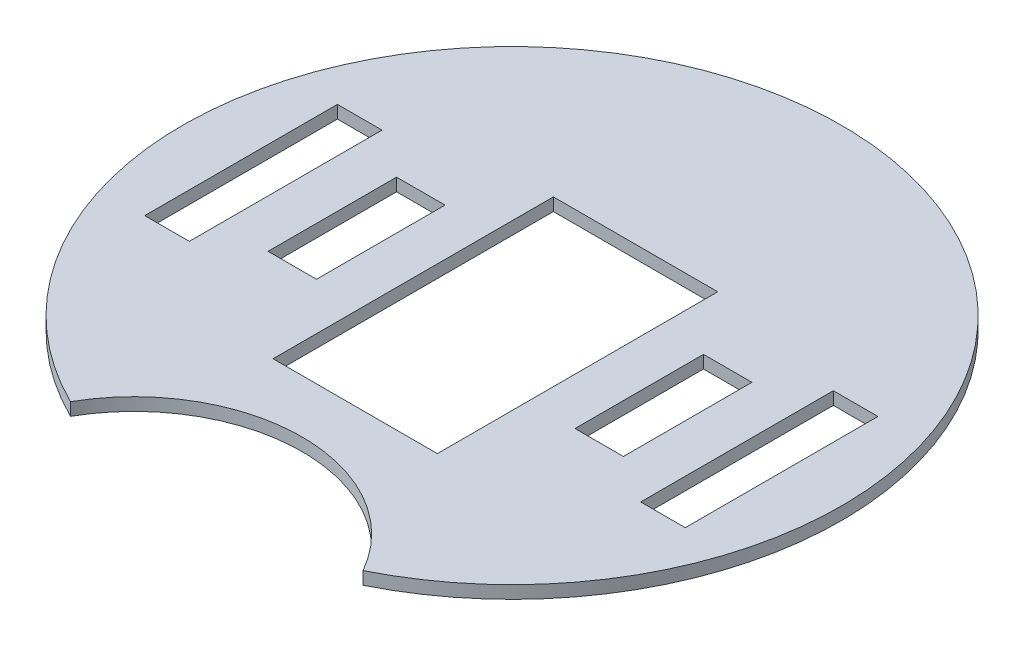
SolidWorks part; units mm, degrees
ref_plane "Front Plane" through (0, 0, 0) normal (0, 0, 1) x (1, 0, 0)
ref_plane "Top Plane" through (0, 0, 0) normal (0, 1, 0) x (1, 0, 0)
ref_plane "Right Plane" through (0, 0, 0) normal (1, 0, 0) x (0, 0, -1)
sketch "Sketch1" plane through (0, 0, 0) normal (0, 1, 0) x (1, 0, 0)
  line L0 (0, -86.0416) -> (-33.2911, -67.2064) construction
  line L1 (0, -86.0416) -> (0, 0) construction
  arc A0 (33.2911, -67.2064) -> (-33.2911, -67.2064) centre (0, 0) ccw
  arc A1 (33.2911, -67.2064) -> (-33.2911, -67.2064) centre (0, -86.0416) ccw
  dimension "D1" = 150
  dimension "D2" = 76.5
  dimension "D3" = 60.5
extrude "Boss-Extrude1" add sketch "Sketch1" along normal blind 2.9
sketch "solenoid placement" plane through (0, 2.9, 0) normal (0, 1, 0) x (1, 0, 0)
  line L0 (0, 0) -> (0, -36) construction
  line L1 (0, -36) -> (0, -47.7916) construction
  line L2 (-19, -36) -> (19, -36) construction
  line L3 (-19, -36) -> (-19, 28.4) construction
  line L4 (-19, 28.4) -> (19, 28.4) construction
  line L5 (19, -36) -> (19, 28.4) construction
  line L6 (-18.7, 28.1) -> (18.7, 28.1)
  line L7 (18.7, -35.7) -> (18.7, 28.1)
  line L8 (-18.7, -35.7) -> (18.7, -35.7)
  line L9 (-18.7, -35.7) -> (-18.7, 28.1)
  circle A1 centre (0, 0) radius 75 construction
  arc A2 (33.2911, -67.2064) -> (-33.2911, -67.2064) centre (0, 0) ccw construction
  arc A3 (33.2911, -67.2064) -> (-33.2911, -67.2064) centre (0, -86.0416) ccw construction
  dimension "D1" = 64.4
  dimension "D2" = 36
  dimension "D3" = 0.3
  dimension "D4" = 38
extrude "Cut-Extrude1" cut sketch "solenoid placement" against normal through all
sketch "Sketch2" plane through (0, 2.9, 0) normal (0, 1, 0) x (1, 0, 0)
  line L0 (51.6584, -21.7893) -> (51.6584, 21.4576) construction
  line L1 (-61.2078, -21.7893) -> (-51.6584, -21.7893) construction
  line L2 (-61.2078, -21.7893) -> (-61.2078, 21.4576) construction
  line L3 (-61.2078, 21.4576) -> (-51.6584, 21.4576) construction
  line L4 (-51.6584, -21.7893) -> (-51.6584, 21.4576) construction
  line L5 (61.2078, 21.4576) -> (51.6584, 21.4576) construction
  line L6 (61.2078, -21.7893) -> (61.2078, 21.4576) construction
  line L7 (61.2078, -21.7893) -> (51.6584, -21.7893) construction
  line L8 (61.5078, -22.0893) -> (61.5078, 21.7576)
  line L9 (61.5078, -22.0893) -> (51.3584, -22.0893)
  line L10 (51.3584, -22.0893) -> (51.3584, 21.7576)
  line L11 (61.5078, 21.7576) -> (51.3584, 21.7576)
  line L12 (0, 0) -> (0, 75) construction
  line L13 (-61.5078, 21.7576) -> (-51.3584, 21.7576)
  line L14 (-51.3584, -22.0893) -> (-51.3584, 21.7576)
  line L15 (-61.5078, -22.0893) -> (-51.3584, -22.0893)
  line L16 (-61.5078, -22.0893) -> (-61.5078, 21.7576)
  arc A0 (33.2911, -67.2064) -> (-33.2911, -67.2064) centre (0, 0) ccw construction
extrude "Cut-Extrude2" cut sketch "Sketch2" against normal through all
sketch "Sketch3" plane through (0, 2.9, 0) normal (0, 1, 0) x (1, 0, 0)
  line L0 (-40.4368, -15.0893) -> (-29.4137, -15.0893)
  line L1 (-40.7368, -15.3893) -> (-29.1137, -15.3893) construction
  line L2 (-40.7368, -15.3893) -> (-40.7368, 14.4493) construction
  line L3 (-40.7368, 14.4493) -> (-29.1137, 14.4493) construction
  line L4 (-29.1137, -15.3893) -> (-29.1137, 14.4493) construction
  line L5 (-29.4137, -15.0893) -> (-29.4137, 14.1493)
  line L6 (-40.4368, 14.1493) -> (-29.4137, 14.1493)
  line L7 (-40.4368, -15.0893) -> (-40.4368, 14.1493)
  line L8 (0, 0) -> (0, 75) construction
  line L9 (29.1137, -15.3893) -> (29.1137, 14.4493) construction
  line L10 (40.7368, 14.4493) -> (29.1137, 14.4493) construction
  line L11 (40.7368, -15.3893) -> (40.7368, 14.4493) construction
  line L12 (40.7368, -15.3893) -> (29.1137, -15.3893) construction
  line L13 (40.4368, -15.0893) -> (40.4368, 14.1493)
  line L14 (40.4368, 14.1493) -> (29.4137, 14.1493)
  line L15 (29.4137, -15.0893) -> (29.4137, 14.1493)
  line L16 (40.4368, -15.0893) -> (29.4137, -15.0893)
  arc A0 (33.2911, -67.2064) -> (-33.2911, -67.2064) centre (0, 0) ccw construction
  point P16 (0, 0)
  point P17 (0, 0)
  point P26 (0, 0)
  point P27 (0, 0)
  point P28 (0, 0)
  point P29 (0, 0)
  point P30 (0, 0)
  point P31 (0, 0)
  point P32 (-40.1435, -14.5813)
  point P34 (0, 0)
  point P35 (-28.0046, 15.6931)
extrude "Cut-Extrude3" cut sketch "Sketch3" against normal through all
equation "\"smallPulleyTeeth\"= 15"
equation "\"largePulleyTeeth\"= 30"
equation "\"eighthThick\"= 2.9mm"
equation "\"sixteenthThick\" = 1.7mm"
equation "\"wheelEighthThick\"=3.0mm"
equation "\"quarterThick\"=5.6mm"
equation "\"OD\" = 150mm"
equation "\"puckAngle\" = 60.5deg"
equation "\"D1@Sketch1\"=\"OD\""
equation "\"puckDiam\" = 76.5mm"
equation "\"D2@Sketch1\"=\"puckDiam\""
equation "\"D3@Sketch1\"=\"puckAngle\""
equation "\"D1@Boss-Extrude1\"=\"eighthThick\""
equation "\"axlePress\" = 5.8mm"
equation "\"press\" = 0.3mm"
equation "\"D1@Sketch3\"=\"press\""
equation "\"wheelClear\" = 0.3mm"
equation "\"D1@Sketch2\"=\"wheelClear\""
